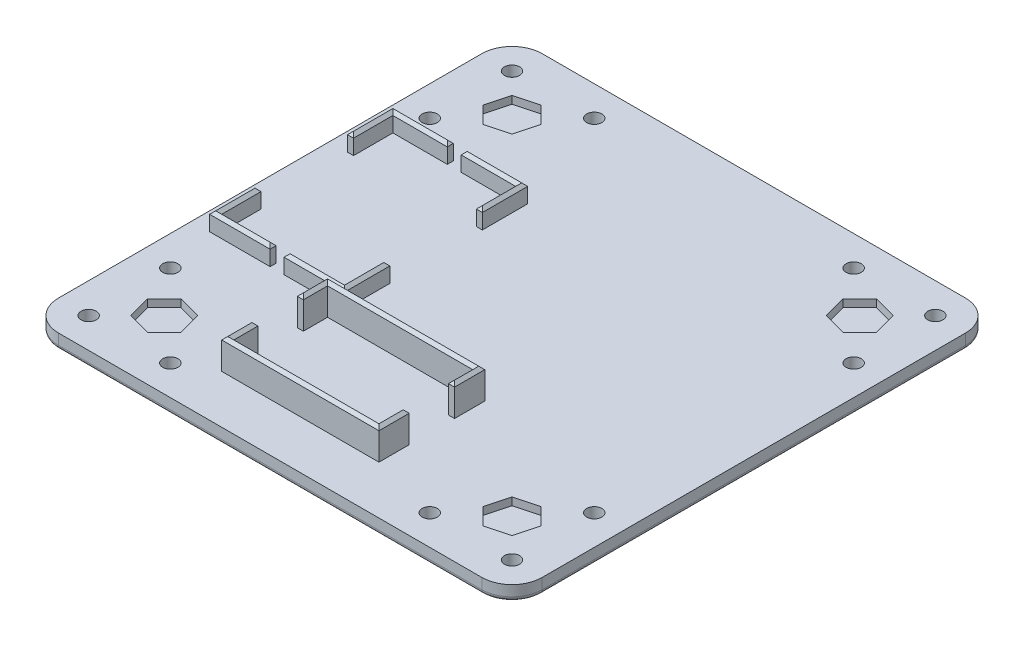
SolidWorks part; units mm, degrees
ref_plane "Front Plane" through (0, 0, 0) normal (0, 0, 1) x (1, 0, 0)
ref_plane "Top Plane" through (0, 0, 0) normal (0, 1, 0) x (1, 0, 0)
ref_plane "Right Plane" through (0, 0, 0) normal (1, 0, 0) x (0, 0, -1)
sketch "Sketch1" plane through (0, 0, 0) normal (0, 1, 0) x (1, 0, 0)
  line L1 (0, 0) -> (203.2, 0)
  line L2 (0, 0) -> (0, 203.2)
  line L3 (0, 203.2) -> (203.2, 203.2)
  line L4 (203.2, 0) -> (203.2, 203.2)
  dimension "D1" = 203.2
  dimension "D2" = 203.2
extrude "Boss-Extrude1" add sketch "Sketch1" along normal blind 6.35
fillet "Fillet1" radius 12.7 4 edges at (0, 3.175, -203.2) (0, 3.175, 0) (203.2, 3.175, 0) (203.2, 3.175, -203.2)
sketch "Sketch2" plane through (0, 0, 0) normal (0, -1, 0) x (1, 0, 0)
  circle A0 centre (12.7, -12.7) radius 3.175
  circle A1 centre (190.5, -12.7) radius 3.175
  circle A2 centre (190.5, -190.5) radius 3.175
  circle A3 centre (12.7, -190.5) radius 3.175
  arc A4 (190.5, -203.2) -> (203.2, -190.5) centre (190.5, -190.5) ccw construction
  arc A5 (12.7, 0) -> (0, -12.7) centre (12.7, -12.7) ccw construction
  dimension "D1" = 6.35
extrude "Cut-Extrude1" cut sketch "Sketch2" against normal through all
sketch "Sketch22" plane through (0, 6.35, 0) normal (0, 1, 0) x (1, 0, 0)
  line L17 (190.5, 203.2) -> (12.7, 203.2) construction
  line L18 (203.2, 12.7) -> (203.2, 190.5) construction
  line L21 (181.6542, 181.6542) -> (172.0521, 184.2271)
  line L22 (172.0521, 184.2271) -> (165.0229, 177.1979)
  line L23 (165.0229, 177.1979) -> (167.5958, 167.5958)
  line L24 (167.5958, 167.5958) -> (177.1979, 165.0229)
  line L25 (177.1979, 165.0229) -> (184.2271, 172.0521)
  line L26 (184.2271, 172.0521) -> (181.6542, 181.6542)
  line L27 (174.625, 174.625) -> (190.5, 190.5) construction
  line L28 (101.6, 203.2) -> (101.6, 0) construction
  line L29 (12.7, 0) -> (190.5, 0) construction
  line L30 (203.2, 101.6) -> (0, 101.6) construction
  line L31 (0, 190.5) -> (0, 12.7) construction
  line L32 (28.575, 174.625) -> (12.7, 190.5) construction
  line L33 (18.9729, 172.0521) -> (21.5458, 181.6542)
  line L34 (26.0021, 165.0229) -> (18.9729, 172.0521)
  line L35 (35.6042, 167.5958) -> (26.0021, 165.0229)
  line L36 (38.1771, 177.1979) -> (35.6042, 167.5958)
  line L37 (31.1479, 184.2271) -> (38.1771, 177.1979)
  line L38 (21.5458, 181.6542) -> (31.1479, 184.2271)
  line L39 (174.625, 28.575) -> (190.5, 12.7) construction
  line L40 (184.2271, 31.1479) -> (181.6542, 21.5458)
  line L41 (177.1979, 38.1771) -> (184.2271, 31.1479)
  line L42 (167.5958, 35.6042) -> (177.1979, 38.1771)
  line L43 (165.0229, 26.0021) -> (167.5958, 35.6042)
  line L44 (172.0521, 18.9729) -> (165.0229, 26.0021)
  line L45 (181.6542, 21.5458) -> (172.0521, 18.9729)
  line L46 (28.575, 28.575) -> (12.7, 12.7) construction
  line L47 (21.5458, 21.5458) -> (31.1479, 18.9729)
  line L48 (31.1479, 18.9729) -> (38.1771, 26.0021)
  line L49 (38.1771, 26.0021) -> (35.6042, 35.6042)
  line L50 (35.6042, 35.6042) -> (26.0021, 38.1771)
  line L51 (26.0021, 38.1771) -> (18.9729, 31.1479)
  line L52 (18.9729, 31.1479) -> (21.5458, 21.5458)
  circle A0 centre (174.625, 174.625) radius 8.609 construction
  circle A1 centre (28.575, 174.625) radius 8.609 construction
  circle A2 centre (174.625, 28.575) radius 8.609 construction
  circle A3 centre (28.575, 28.575) radius 8.609 construction
  dimension "D5" = 17.218
  dimension "D3" = 28.575
  dimension "D4" = 28.575
extrude "Cut-Extrude2" cut sketch "Sketch22" against normal blind 3.175
sketch "Sketch23" plane through (0, 6.35, 0) normal (0, 1, 0) x (1, 0, 0)
  line L1 (64.262, 145.542) -> (38.862, 145.542)
  line L2 (64.262, 145.542) -> (64.262, 126.492)
  line L3 (64.262, 68.58) -> (38.862, 68.58)
  line L4 (7.62, 145.542) -> (7.62, 126.492)
  line L5 (7.62, 145.542) -> (7.62, 203.2) construction
  line L6 (190.5, 203.2) -> (12.7, 203.2) construction
  line L7 (7.62, 68.58) -> (7.62, 0) construction
  line L8 (12.7, 0) -> (190.5, 0) construction
  line L9 (33.02, 145.542) -> (33.02, 143.002)
  line L10 (61.722, 143.002) -> (38.862, 143.002)
  line L11 (61.722, 143.002) -> (61.722, 126.492)
  line L12 (61.722, 71.12) -> (38.862, 71.12)
  line L13 (10.16, 143.002) -> (10.16, 126.492)
  line L14 (38.862, 145.542) -> (38.862, 143.002)
  line L15 (64.262, 126.492) -> (61.722, 126.492)
  line L16 (64.262, 87.63) -> (61.722, 87.63)
  line L17 (10.16, 126.492) -> (7.62, 126.492)
  line L18 (10.16, 87.63) -> (7.62, 87.63)
  line L19 (33.02, 71.12) -> (33.02, 68.58)
  line L20 (38.862, 71.12) -> (38.862, 68.58)
  line L21 (33.02, 145.542) -> (7.62, 145.542)
  line L22 (33.02, 143.002) -> (10.16, 143.002)
  line L23 (64.262, 87.63) -> (64.262, 68.58)
  line L24 (61.722, 87.63) -> (61.722, 71.12)
  line L25 (33.02, 71.12) -> (10.16, 71.12)
  line L26 (33.02, 68.58) -> (7.62, 68.58)
  line L27 (10.16, 87.63) -> (10.16, 71.12)
  line L28 (7.62, 87.63) -> (7.62, 68.58)
  line L29 (0, 190.5) -> (0, 12.7) construction
  point P32 (33.02, 144.272)
  dimension "D2" = 71.882
  dimension "D3" = 51.562
  dimension "D4" = 2.54
  dimension "D5" = 2.54
  dimension "D6" = 2.54
  dimension "D7" = 2.54
  dimension "D8" = 19.05
  dimension "D9" = 19.05
  dimension "D10" = 25.4
  dimension "D11" = 25.4
  dimension "D12" = 19.05
  dimension "D13" = 19.05
  dimension "D14" = 25.4
  dimension "D15" = 25.4
  dimension "D17" = 7.62
  dimension "D18" = 134.62
extrude "Boss-Extrude2" add sketch "Sketch23" along normal blind 7.62
chamfer "Chamfer1" distance 1.27 angle 45 24 edges at (8.89, 13.97, -87.63) (10.16, 13.97, -79.375) (21.59, 13.97, -71.12) (33.02, 13.97, -69.85) (20.32, 13.97, -68.58) (7.62, 13.97, -78.105) (51.562, 13.97, -68.58) (38.862, 13.97, -69.85) (50.292, 13.97, -71.12) (61.722, 13.97, -79.375) (62.992, 13.97, -87.63) (64.262, 13.97, -78.105) (62.992, 13.97, -126.492) (61.722, 13.97, -134.747) (50.292, 13.97, -143.002) (38.862, 13.97, -144.272) (51.562, 13.97, -145.542) (64.262, 13.97, -136.017) (33.02, 13.97, -144.272) (21.59, 13.97, -143.002) (10.16, 13.97, -134.747) (8.89, 13.97, -126.492) (7.62, 13.97, -136.017) (20.32, 13.97, -145.542)
sketch "Sketch24" plane through (0, 6.35, 0) normal (0, 1, 0) x (1, 0, 0)
  line L0 (12.7, 0) -> (190.5, 0) construction
  line L1 (124.46, 62.23) -> (63.5, 62.23)
  line L2 (124.46, 62.23) -> (124.46, 52.07)
  line L3 (124.46, 22.86) -> (63.5, 22.86)
  line L4 (63.5, 62.23) -> (63.5, 52.07)
  line L5 (0, 190.5) -> (0, 12.7) construction
  line L6 (127, 64.77) -> (60.96, 64.77)
  line L7 (127, 64.77) -> (127, 52.07)
  line L8 (127, 20.32) -> (60.96, 20.32)
  line L9 (60.96, 64.77) -> (60.96, 52.07)
  line L10 (60.96, 52.07) -> (63.5, 52.07)
  line L11 (60.96, 33.02) -> (63.5, 33.02)
  line L12 (60.96, 33.02) -> (60.96, 20.32)
  line L13 (63.5, 33.02) -> (63.5, 22.86)
  line L14 (124.46, 52.07) -> (127, 52.07)
  line L15 (124.46, 33.02) -> (127, 33.02)
  line L16 (124.46, 33.02) -> (124.46, 22.86)
  line L17 (127, 33.02) -> (127, 20.32)
  dimension "D1" = 39.37
  dimension "D2" = 60.96
  dimension "D3" = 22.86
  dimension "D4" = 2.54
  dimension "D5" = 2.54
  dimension "D6" = 2.54
  dimension "D7" = 2.54
  dimension "D8" = 63.5
  dimension "D9" = 12.7
  dimension "D10" = 12.7
extrude "Boss-Extrude3" add sketch "Sketch24" along normal blind 12.7
chamfer "Chamfer2" distance 1.27 angle 45 16 edges at (93.98, 19.05, -62.23) (63.5, 19.05, -57.15) (62.23, 19.05, -52.07) (60.96, 19.05, -58.42) (93.98, 19.05, -64.77) (127, 19.05, -58.42) (93.98, 19.05, -20.32) (60.96, 19.05, -26.67) (62.23, 19.05, -33.02) (63.5, 19.05, -27.94) (93.98, 19.05, -22.86) (124.46, 19.05, -57.15) (125.73, 19.05, -52.07) (124.46, 19.05, -27.94) (125.73, 19.05, -33.02) (127, 19.05, -26.67)
fillet "Fillet2" radius 1.905 12 edges at (3.7197, 0, -3.7197) (101.6, 0, 0) (199.4803, 0, -3.7197) (203.2, 0, -101.6) (199.4803, 0, -199.4803) (101.6, 0, -203.2) (3.7197, 0, -199.4803) (0, 0, -101.6) (12.7, 0, -15.875) (190.5, 0, -15.875) (190.5, 0, -193.675) (12.7, 0, -193.675)
sketch "Sketch27" plane through (0, 6.35, 0) normal (0, 1, 0) x (1, 0, 0)
  line L0 (38.862, 143.002) -> (61.722, 143.002) construction
  line L1 (85.852, 143.002) -> (137.414, 143.002)
  line L2 (85.852, 143.002) -> (85.852, 129.032)
  line L3 (85.852, 71.12) -> (137.414, 71.12)
  line L4 (137.414, 143.002) -> (137.414, 129.032)
  line L5 (83.312, 145.542) -> (83.312, 129.032)
  line L6 (83.312, 68.58) -> (139.954, 68.58)
  line L7 (139.954, 145.542) -> (139.954, 129.032)
  line L8 (83.312, 145.542) -> (139.954, 145.542)
  line L9 (83.312, 129.032) -> (85.852, 129.032)
  line L10 (83.312, 90.17) -> (85.852, 90.17)
  line L11 (137.414, 90.17) -> (139.954, 90.17)
  line L12 (139.954, 129.032) -> (137.414, 129.032)
  line L13 (83.312, 90.17) -> (83.312, 68.58)
  line L14 (83.312, 145.542) -> (83.312, 68.58) construction
  line L15 (85.852, 90.17) -> (85.852, 71.12)
  line L16 (85.852, 143.002) -> (85.852, 71.12) construction
  line L17 (137.414, 90.17) -> (137.414, 71.12)
  line L18 (137.414, 143.002) -> (137.414, 71.12) construction
  line L19 (139.954, 90.17) -> (139.954, 68.58)
  line L20 (139.954, 145.542) -> (139.954, 68.58) construction
  line L21 (64.262, 68.58) -> (64.262, 87.63) construction
  dimension "D1" = 71.882
  dimension "D2" = 51.562
  dimension "D4" = 19.05
  dimension "D3" = 2.54
sketch "Sketch28" plane through (0, 6.35, 0) normal (0, 1, 0) x (1, 0, 0)
  line L0 (190.5, 203.2) -> (12.7, 203.2) construction
  line L1 (203.2, 12.7) -> (203.2, 190.5) construction
  line L2 (12.7, 0) -> (190.5, 0) construction
  line L4 (0, 190.5) -> (0, 12.7) construction
  circle A0 centre (47.117, 190.627) radius 3.175
  circle A1 centre (156.083, 190.627) radius 3.175
  circle A2 centre (190.627, 156.083) radius 3.175
  circle A3 centre (190.627, 47.117) radius 3.175
  circle A4 centre (156.083, 12.573) radius 3.175
  circle A5 centre (47.117, 12.573) radius 3.175
  circle A6 centre (12.573, 156.083) radius 3.175
  circle A7 centre (12.573, 47.117) radius 3.175
  point P24 (0, 0)
  point P25 (0, 0)
  point P26 (0, 0)
  point P27 (0, 0)
  point P28 (0, 0)
  point P29 (0, 0)
  dimension "D4" = 6.35
  dimension "D1" = 12.573
  dimension "D2" = 12.573
  dimension "D3" = 12.573
  dimension "D5" = 12.573
  dimension "D6" = 47.117
  dimension "D7" = 47.117
  dimension "D8" = 47.117
  dimension "D9" = 47.117
extrude "Cut-Extrude3" cut sketch "Sketch28" against normal through all
